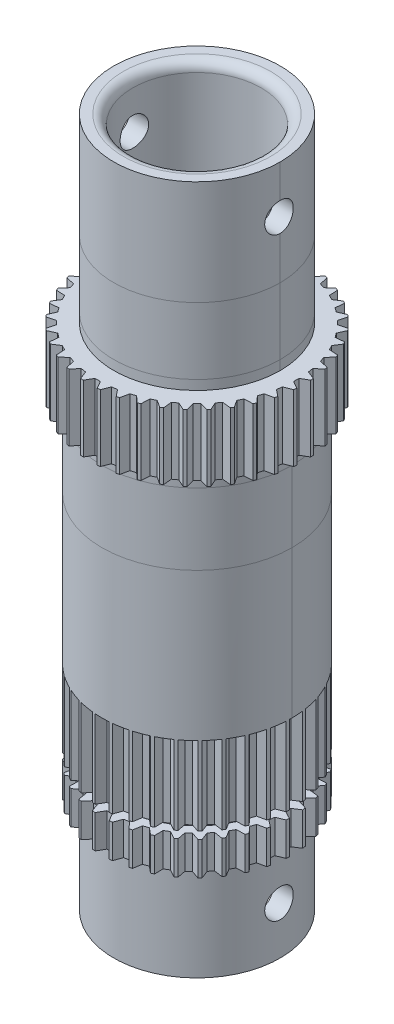
SolidWorks part; units mm, degrees
material "AISI 4130 Steel, normalized at 870C"
ref_plane "Front Plane" through (0, 0, 0) normal (0, 0, 1) x (1, 0, 0)
ref_plane "Top Plane" through (0, 0, 0) normal (0, 1, 0) x (1, 0, 0)
ref_plane "Right Plane" through (0, 0, 0) normal (1, 0, 0) x (0, 0, -1)
sketch "Sketch1" plane through (0, 0, 0) normal (0, 0, 1) x (1, 0, 0)
  line L0 (0, 83.8718) -> (0, -77.4105) construction
  line L1 (0, -72.5) -> (-20, -72.5)
  line L2 (-20, -72.5) -> (-20, 72.5)
  line L3 (-20, 72.5) -> (0, 72.5)
  line L4 (-91.4513, 0) -> (111.5805, 0) construction
  line L5 (0, -72.5) -> (0, 72.5)
  line L6 (0, 72.5) -> (0, -72.5)
  dimension "D1" = 145
  dimension "D2" = 20
revolve "Revolve1" add sketch "Sketch1" angle 360 about L0 region at (-10, 0, 0)
sketch "Sketch2" plane through (0, -72.5, 0) normal (0, -1, 0) x (1, 0, 0)
  circle A0 centre (0, 0) radius 13.5
  dimension "D1" = 27
extrude "Cut-Extrude1" cut sketch "Sketch2" against normal through all
sketch "Sketch3" plane through (0, 0, 0) normal (1, 0, 0) x (0, 0, -1)
  line L0 (40.074, 50.5) -> (-35.4941, 50.5)
  line L1 (41.0169, 36.5) -> (-35.4941, 36.5)
  line L2 (41.0169, 34.5) -> (-35.4941, 34.5)
  line L3 (41.0169, 20.5) -> (-35.4941, 20.5)
  line L4 (41.0169, 18.5) -> (-35.4941, 18.5)
  line L5 (41.0169, 3.5) -> (-35.4941, 3.5)
  line L6 (20, 72.5) -> (-20, 72.5) construction
  line L7 (0, -72.5) -> (0, 72.5)
  line L8 (-20, -72.5) -> (20, -72.5) construction
  dimension "D1" = 22
  dimension "D2" = 14
  dimension "D3" = 2
  dimension "D4" = 14
  dimension "D5" = 2
  dimension "D6" = 15
split line "Split Line1"
ref_plane "Plane1" through (0, 34.5, 0) normal (0, 1, 0) x (1, 0, 0)
sketch "Sketch4" plane through (0, 34.5, 0) normal (0, 1, 0) x (1, 0, 0)
  circle A0 centre (0, 0) radius 20
  circle A1 centre (0, 0) radius 22.5
  dimension "D1" = 45
  dimension "D2" = 40
extrude "Boss-Extrude1" add sketch "Sketch4" against normal blind 14
sketch "Sketch5" plane through (0, 34.5, 0) normal (0, 1, 0) x (1, 0, 0)
  line L0 (0, 0) -> (0, 27.8267) construction
  line L1 (0.5617, 20.8821) -> (-0.5617, 20.8821)
  line L2 (-0.5617, 20.8821) -> (-1.4681, 22.4521)
  line L3 (-1.4681, 21.4421) -> (2.5415, 21.4421) construction
  line L4 (0.5617, 20.8821) -> (1.4681, 22.4521)
  arc A0 (1.4681, 22.4521) -> (-1.4681, 22.4521) centre (0, 0) ccw
  point P10 (-0.885, 21.4421)
  point P11 (0, 20.8821)
  dimension "D1" = 30
  dimension "D5" = 22.5
  dimension "D2" = 1.01
  dimension "D3" = 0.56
  dimension "D4" = 0.885
extrude "Cut-Extrude2" cut sketch "Sketch5" against normal through all
pattern_circular "CirPattern1" count 40 over 360 about axis through (0, 72.5, 0) along (0, -1, 0) of "Cut-Extrude2"
ref_plane "Plane2" through (0, -57.5, 0) normal (0, -1, 0) x (-1, 0, 0)
sketch "Sketch6" plane through (0, -57.5, 0) normal (0, -1, 0) x (-1, 0, 0)
  circle A0 centre (0, 0) radius 13.5
  circle A1 centre (0, 0) radius 11.5
  dimension "D1" = 27
  dimension "D2" = 23
extrude "Boss-Extrude2" add sketch "Sketch6" against normal blind 103
sketch "Sketch7" plane through (0, -57.5, 0) normal (0, -1, 0) x (1, 0, 0)
  line L0 (0, 15.3737) -> (0, 0) construction
  line L1 (1.4681, 11.4059) -> (0.5617, 12.9759)
  line L2 (0.5617, 12.9759) -> (-0.5617, 12.9759)
  line L3 (0.885, 12.4159) -> (-0.885, 12.4159) construction
  line L4 (-1.4681, 11.4059) -> (-0.5617, 12.9759)
  arc A0 (1.4681, 11.4059) -> (-1.4681, 11.4059) centre (0, 0) ccw
  point P10 (0, 12.9759)
  dimension "D1" = 23
  dimension "D2" = 1.01
  dimension "D3" = 0.56
  dimension "D4" = 1.77
  dimension "D5" = 30
extrude "Cut-Extrude3" cut sketch "Sketch7" against normal through all
pattern_circular "CirPattern2" count 20 over 360 about axis through (0, -72.5, 0) along (0, -1, 0) of "Cut-Extrude3"
fillet "Fillet1" radius 2 2 edges at (0, 72.5, -13.5) (0, -72.5, -13.5)
sketch "Sketch8" plane through (0, -72.5, 0) normal (0, -1, 0) x (1, 0, 0)
  circle A0 centre (0, 0) radius 17.5
  dimension "D1" = 35
extrude "Cut-Extrude4" cut sketch "Sketch8" against normal blind 20 flip side to cut
sketch "Sketch9" plane through (0, -52.5, 0) normal (0, -1, 0) x (1, 0, 0)
  line L0 (0, 0) -> (0, 22.9601) construction
  line L5 (0.5667, 18.3757) -> (1.4731, 19.9457)
  line L6 (0.5667, 18.3757) -> (-0.5667, 18.3757)
  line L7 (-0.5667, 18.3757) -> (-1.4731, 19.9457)
  arc A2 (1.4731, 19.9457) -> (-1.4731, 19.9457) centre (0, 0) ccw
  arc A3 (20, 0) -> (-20, 0) centre (0, 0) ccw construction
  dimension "D1" = 30
extrude "Cut-Extrude5" cut sketch "Sketch9" against normal blind 25
pattern_circular "CirPattern3" count 35 over 360 about axis through (0, -52.5, 0) along (0, -1, 0) of "Cut-Extrude5" reverse direction yes
ref_plane "Plane3" through (0, -45.5, 0) normal (0, -1, 0) x (-1, 0, 0)
sketch "Sketch10" plane through (0, -45.5, 0) normal (0, -1, 0) x (-1, 0, 0)
  circle A2 centre (0, 0) radius 20
  circle A7 centre (0, 0) radius 16.5
  circle A8 centre (0, 0) radius 17.5 construction
  dimension "D1" = 40
  dimension "D2" = 1
extrude "Cut-Extrude6" cut sketch "Sketch10" against normal blind 1.5
sketch "Sketch11" plane through (0, 72.5, 0) normal (0, 1, 0) x (1, 0, 0)
  circle A0 centre (0, 0) radius 17.5
  circle A1 centre (0, 0) radius 20
  dimension "D1" = 35
  dimension "D2" = 40
extrude "Cut-Extrude7" cut sketch "Sketch11" against normal blind 38
sketch "Sketch12" plane through (0, 0, 0) normal (1, 0, 0) x (0, 0, -1)
  line L0 (0, 36.5) -> (0, 72.5)
  line L1 (17.5, 72.5) -> (-17.5, 72.5) construction
  line L2 (36.3023, 36.5) -> (-32.1266, 36.5)
  line L3 (36.3023, 50.5) -> (-32.1266, 50.5)
  line L4 (17.5, 34.5) -> (-17.5, 34.5) construction
  line L5 (0, 34.5) -> (0, 36.5)
  point P9 (0, 34.5)
  dimension "D1" = 22
  dimension "D2" = 14
split line "Split Line2"
sketch "Sketch13" plane through (0, 0, 0) normal (1, 0, 0) x (0, 0, -1)
  line L1 (-17.5, -72.5) -> (17.5, -72.5) construction
  line L2 (0, 72.5) -> (0, 50.5) construction
  line L3 (15.5, 72.5) -> (-15.5, 72.5) construction
  circle A1 centre (0, -62.5) radius 3
  circle A2 centre (0, 62.5) radius 3
  dimension "D1" = 6
  dimension "D2" = 6
  dimension "D3" = 10
  dimension "D4" = 10
extrude "Cut-Extrude8" cut sketch "Sketch13" against normal through all both and the other way through all
ref_plane "Plane4" through (0, 0, 0) normal (0, -1, 0) x (-1, 0, 0)
